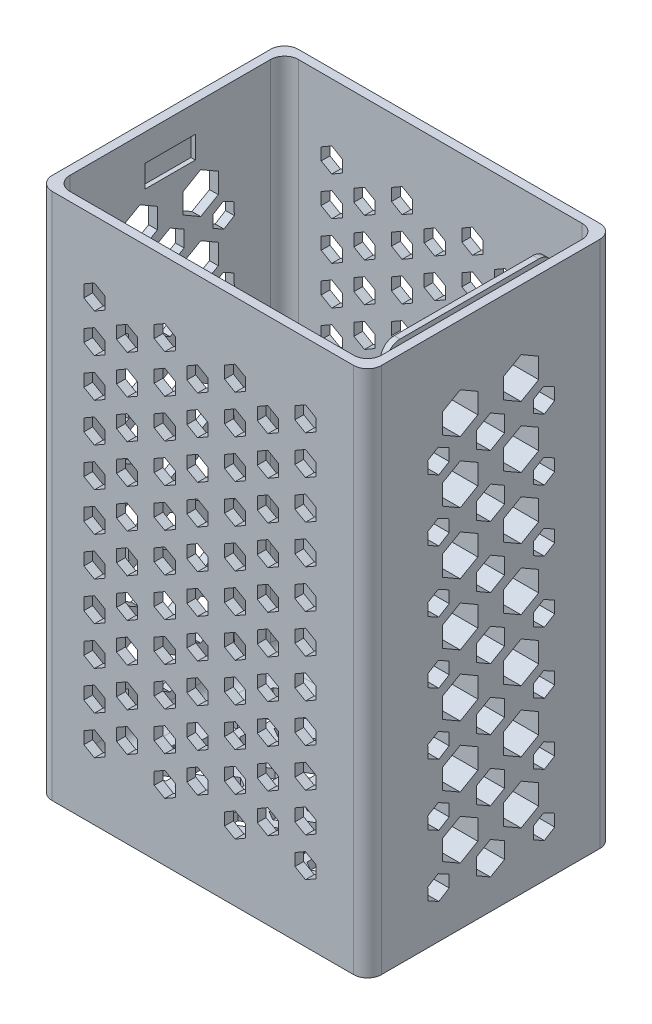
SolidWorks part; units mm, degrees
ref_plane "Front Plane" through (0, 0, 0) normal (0, 0, 1) x (1, 0, 0)
ref_plane "Top Plane" through (0, 0, 0) normal (0, 1, 0) x (1, 0, 0)
ref_plane "Right Plane" through (0, 0, 0) normal (1, 0, 0) x (0, 0, -1)
sketch "Sketch1" plane through (0, 0, 0) normal (0, 1, 0) x (1, 0, 0)
  line L0 (-6.35, 6.35) -> (-6.35, -171.3484)
  line L1 (0, 0) -> (224.9932, 0)
  line L2 (0, 0) -> (0, -164.9984)
  line L3 (0, -164.9984) -> (224.9932, -164.9984)
  line L4 (224.9932, 0) -> (224.9932, -164.9984)
  line L5 (-6.35, -171.3484) -> (231.3432, -171.3484)
  line L6 (231.3432, 6.35) -> (231.3432, -171.3484)
  line L7 (-6.35, 6.35) -> (231.3432, 6.35)
  dimension "D1" = 224.9932
  dimension "D2" = 164.9984
  dimension "D3" = 6.35
extrude "Boss-Extrude1" add sketch "Sketch1" along normal blind 374.65
sketch "Sketch4" plane through (224.9932, 0, 0) normal (-1, 0, 0) x (0, 0, 1)
  line L0 (164.9984, 0) -> (0, 0) construction
  line L1 (28.7274, 0) -> (136.1694, 0)
  line L2 (28.7274, 0) -> (28.7274, 374.65)
  line L3 (28.7274, 374.65) -> (136.1694, 374.65)
  line L4 (136.1694, 0) -> (136.1694, 374.65)
  line L5 (164.9984, 374.65) -> (0, 374.65) construction
  line L8 (164.9984, 374.65) -> (164.9984, 0) construction
  dimension "D1" = 107.442
  dimension "D2" = 28.829
extrude "Boss-Extrude2" add sketch "Sketch4" along normal blind 9.017
sketch "Sketch5" plane through (215.9762, 0, 0) normal (-1, 0, 0) x (0, 0, 1)
  line L0 (136.1694, 374.65) -> (28.7274, 374.65) construction
  line L5 (142.5194, 0) -> (22.3774, 0)
  line L6 (142.5194, 0) -> (142.5194, 374.65)
  line L7 (142.5194, 374.65) -> (22.3774, 374.65)
  line L8 (22.3774, 0) -> (22.3774, 374.65)
  line L9 (28.7274, 0) -> (136.1694, 0) construction
  line L11 (164.9984, 374.65) -> (164.9984, 0) construction
  line L12 (136.1694, 0) -> (136.1694, 374.65) construction
  line L13 (28.7274, 374.65) -> (28.7274, 0) construction
  dimension "D1" = 6.35
  dimension "D2" = 6.35
extrude "Boss-Extrude3" add sketch "Sketch5" along normal blind 4.191
sketch "Sketch7" plane through (0, 374.65, 0) normal (0, 1, 0) x (1, 0, 0)
  line L1 (215.9762, -136.1694) -> (224.9932, -136.1694)
  line L2 (215.9762, -136.1694) -> (215.9762, -28.7274)
  line L3 (215.9762, -28.7274) -> (224.9932, -28.7274)
  line L4 (224.9932, -136.1694) -> (224.9932, -28.7274)
extrude "Cut-Extrude1" cut sketch "Sketch7" against normal blind 21.59
sketch "Sketch10" plane through (0, 374.65, 0) normal (0, 1, 0) x (1, 0, 0)
  line L1 (211.7852, -142.5194) -> (215.9762, -142.5194)
  line L2 (211.7852, -142.5194) -> (211.7852, -22.3774)
  line L3 (211.7852, -22.3774) -> (215.9762, -22.3774)
  line L4 (215.9762, -142.5194) -> (215.9762, -22.3774)
extrude "Cut-Extrude2" cut sketch "Sketch10" against normal blind 5.588
fillet "Fillet1" radius 10 1 edges at (231.3432, 187.325, 171.3484)
fillet "Fillet2" radius 10 1 edges at (224.9932, 187.325, 164.9984)
fillet "Fillet3" radius 10 2 edges at (231.3432, 187.325, -6.35) (224.9932, 187.325, 0)
fillet "Fillet4" radius 10 2 edges at (-6.35, 187.325, 171.3484) (0, 187.325, 164.9984)
fillet "Fillet5" radius 10 2 edges at (0, 187.325, 0) (-6.35, 187.325, -6.35)
fillet "Fillet6" radius 10 2 edges at (220.4847, 353.06, 136.1694) (220.4847, 353.06, 28.7274)
fillet "Fillet7" radius 10 2 edges at (213.8807, 369.062, 22.3774) (213.8807, 369.062, 142.5194)
sketch "Sketch11" plane through (211.7852, 0, 0) normal (-1, 0, 0) x (0, 0, 1)
  line L0 (22.3774, 0) -> (142.5194, 0) construction
  line L1 (57.0484, 0) -> (107.8484, 0)
  line L2 (57.0484, 0) -> (57.0484, 15.24)
  line L3 (57.0484, 15.24) -> (107.8484, 15.24)
  line L4 (107.8484, 0) -> (107.8484, 15.24)
  line L5 (142.5194, 0) -> (142.5194, 359.062) construction
  dimension "D1" = 15.24
  dimension "D2" = 50.8
  dimension "D3" = 34.671
extrude "Boss-Extrude4" add sketch "Sketch11" along normal blind 19.9898
fillet "Fillet10" radius 10 2 edges at (191.7954, 7.62, 107.8484) (191.7954, 7.62, 57.0484)
fillet "Fillet11" radius 10 5 edges at (206.7903, 15.24, 107.8484) (194.7243, 15.24, 104.9195) (206.7903, 15.24, 57.0484) (194.7243, 15.24, 59.9773) (191.7954, 15.24, 82.4484)
sketch "Sketch12" plane through (0, 0, 0) normal (0, -1, 0) x (1, 0, 0)
  line L0 (231.3432, 161.3484) -> (231.3432, 3.65) construction
  line L1 (221.3432, -6.35) -> (3.65, -6.35) construction
  line L2 (-6.35, 3.65) -> (-6.35, 161.3484) construction
  line L3 (3.65, 171.3484) -> (221.3432, 171.3484) construction
  line L4 (231.3432, 161.3484) -> (231.3432, 3.65)
  line L5 (221.3432, -6.35) -> (3.65, -6.35)
  line L6 (-6.35, 3.65) -> (-6.35, 161.3484)
  line L7 (3.65, 171.3484) -> (221.3432, 171.3484)
  arc A0 (231.3432, 161.3484) -> (221.3432, 171.3484) centre (221.3432, 161.3484) ccw construction
  arc A1 (221.3432, -6.35) -> (231.3432, 3.65) centre (221.3432, 3.65) ccw construction
  arc A2 (-6.35, 3.65) -> (3.65, -6.35) centre (3.65, 3.65) ccw construction
  arc A3 (3.65, 171.3484) -> (-6.35, 161.3484) centre (3.65, 161.3484) ccw construction
  arc A4 (231.3432, 161.3484) -> (221.3432, 171.3484) centre (221.3432, 161.3484) ccw
  arc A5 (221.3432, -6.35) -> (231.3432, 3.65) centre (221.3432, 3.65) ccw
  arc A6 (-6.35, 3.65) -> (3.65, -6.35) centre (3.65, 3.65) ccw
  arc A7 (3.65, 171.3484) -> (-6.35, 161.3484) centre (3.65, 161.3484) ccw
extrude "Boss-Extrude5" add sketch "Sketch12" along normal blind 6.35
fillet "Fillet13" radius 10 9 edges at (224.9932, 0, 19.3637) (222.0643, 0, 2.9289) (112.4966, 0, 0) (2.9289, 0, 2.9289) (224.9932, 0, 145.5839) (222.0643, 0, 162.0695) (112.4966, 0, 164.9984) (2.9289, 0, 162.0695) (0, 0, 82.4992)
sketch "Sketch13" plane through (0, 0, 0) normal (1, 0, 0) x (0, 0, -1)
  line L0 (-10, 374.65) -> (-154.9984, 374.65) construction
  line L1 (-100.7542, 355.0412) -> (-64.356, 355.0412)
  line L2 (-100.7542, 355.0412) -> (-100.7542, 338.9122)
  line L3 (-100.7542, 338.9122) -> (-64.356, 338.9122)
  line L4 (-64.356, 355.0412) -> (-64.356, 338.9122)
  line L5 (-10, 10) -> (-10, 374.65) construction
  dimension "D1" = 19.6088
  dimension "D2" = 16.129
  dimension "D3" = 36.3982
  dimension "D4" = 54.356
extrude "Cut-Extrude4" cut sketch "Sketch13" against normal blind 3.175
sketch "Sketch15" plane through (0, -6.35, 0) normal (0, -1, 0) x (1, 0, 0)
  line L0 (177.8, 131.1399) -> (184.15, 134.8061)
  line L1 (196.85, 131.1399) -> (203.2, 134.8061)
  line L2 (203.2, 134.8061) -> (203.2, 142.1384)
  line L3 (203.2, 142.1384) -> (196.85, 145.8046)
  line L4 (196.85, 145.8046) -> (190.5, 142.1384)
  line L5 (190.5, 142.1384) -> (190.5, 134.8061)
  line L6 (190.5, 134.8061) -> (196.85, 131.1399)
  line L7 (171.45, 134.8061) -> (177.8, 131.1399)
  line L8 (171.45, 142.1384) -> (171.45, 134.8061)
  line L9 (177.8, 145.8046) -> (171.45, 142.1384)
  line L10 (184.15, 142.1384) -> (177.8, 145.8046)
  line L11 (184.15, 134.8061) -> (184.15, 142.1384)
  line L12 (158.75, 131.1399) -> (165.1, 134.8061)
  line L13 (152.4, 134.8061) -> (158.75, 131.1399)
  line L14 (152.4, 142.1384) -> (152.4, 134.8061)
  line L15 (158.75, 145.8046) -> (152.4, 142.1384)
  line L16 (165.1, 142.1384) -> (158.75, 145.8046)
  line L17 (165.1, 134.8061) -> (165.1, 142.1384)
  line L18 (139.7, 131.1399) -> (146.05, 134.8061)
  line L19 (133.35, 134.8061) -> (139.7, 131.1399)
  line L20 (133.35, 142.1384) -> (133.35, 134.8061)
  line L21 (139.7, 145.8046) -> (133.35, 142.1384)
  line L22 (146.05, 142.1384) -> (139.7, 145.8046)
  line L23 (146.05, 134.8061) -> (146.05, 142.1384)
  line L24 (120.65, 131.1399) -> (127, 134.8061)
  line L25 (114.3, 134.8061) -> (120.65, 131.1399)
  line L26 (114.3, 142.1384) -> (114.3, 134.8061)
  line L27 (120.65, 145.8046) -> (114.3, 142.1384)
  line L28 (127, 142.1384) -> (120.65, 145.8046)
  line L29 (127, 134.8061) -> (127, 142.1384)
  line L30 (-6.35, 161.3484) -> (-6.35, 3.65) construction
  line L31 (231.3432, 3.65) -> (231.3432, 161.3484) construction
  line L32 (3.65, -6.35) -> (221.3432, -6.35) construction
  line L38 (101.6, 131.1399) -> (107.95, 134.8061)
  line L39 (95.25, 134.8061) -> (101.6, 131.1399)
  line L40 (95.25, 142.1384) -> (95.25, 134.8061)
  line L41 (101.6, 145.8046) -> (95.25, 142.1384)
  line L42 (107.95, 142.1384) -> (101.6, 145.8046)
  line L43 (107.95, 134.8061) -> (107.95, 142.1384)
  line L44 (82.55, 131.1399) -> (88.9, 134.8061)
  line L45 (76.2, 134.8061) -> (82.55, 131.1399)
  line L46 (76.2, 142.1384) -> (76.2, 134.8061)
  line L47 (82.55, 145.8046) -> (76.2, 142.1384)
  line L48 (88.9, 142.1384) -> (82.55, 145.8046)
  line L49 (88.9, 134.8061) -> (88.9, 142.1384)
  line L50 (63.5, 131.1399) -> (69.85, 134.8061)
  line L51 (57.15, 134.8061) -> (63.5, 131.1399)
  line L52 (57.15, 142.1384) -> (57.15, 134.8061)
  line L53 (63.5, 145.8046) -> (57.15, 142.1384)
  line L54 (69.85, 142.1384) -> (63.5, 145.8046)
  line L55 (69.85, 134.8061) -> (69.85, 142.1384)
  line L56 (44.45, 131.1399) -> (50.8, 134.8061)
  line L57 (38.1, 134.8061) -> (44.45, 131.1399)
  line L58 (38.1, 142.1384) -> (38.1, 134.8061)
  line L59 (44.45, 145.8046) -> (38.1, 142.1384)
  line L60 (50.8, 142.1384) -> (44.45, 145.8046)
  line L61 (50.8, 134.8061) -> (50.8, 142.1384)
  line L62 (25.4, 131.1399) -> (31.75, 134.8061)
  line L63 (19.05, 134.8061) -> (25.4, 131.1399)
  line L64 (19.05, 142.1384) -> (19.05, 134.8061)
  line L65 (25.4, 145.8046) -> (19.05, 142.1384)
  line L66 (31.75, 142.1384) -> (25.4, 145.8046)
  line L67 (31.75, 134.8061) -> (31.75, 142.1384)
  line L74 (32.4716, 113.2256) -> (38.8216, 116.8918)
  line L75 (26.1216, 116.8918) -> (32.4716, 113.2256)
  line L76 (26.1216, 124.2241) -> (26.1216, 116.8918)
  line L77 (32.4716, 127.8903) -> (26.1216, 124.2241)
  line L78 (38.8216, 124.2241) -> (32.4716, 127.8903)
  line L79 (38.8216, 116.8918) -> (38.8216, 124.2241)
  line L80 (51.5216, 113.2256) -> (57.8716, 116.8918)
  line L81 (57.8716, 116.8918) -> (57.8716, 124.2241)
  line L82 (57.8716, 124.2241) -> (51.5216, 127.8903)
  line L83 (51.5216, 127.8903) -> (45.1716, 124.2241)
  line L84 (45.1716, 124.2241) -> (45.1716, 116.8918)
  line L85 (45.1716, 116.8918) -> (51.5216, 113.2256)
  line L86 (70.5716, 113.2256) -> (76.9216, 116.8918)
  line L87 (76.9216, 116.8918) -> (76.9216, 124.2241)
  line L88 (76.9216, 124.2241) -> (70.5716, 127.8903)
  line L89 (70.5716, 127.8903) -> (64.2216, 124.2241)
  line L90 (64.2216, 124.2241) -> (64.2216, 116.8918)
  line L91 (64.2216, 116.8918) -> (70.5716, 113.2256)
  line L92 (89.6216, 113.2256) -> (95.9716, 116.8918)
  line L93 (95.9716, 116.8918) -> (95.9716, 124.2241)
  line L94 (95.9716, 124.2241) -> (89.6216, 127.8903)
  line L95 (89.6216, 127.8903) -> (83.2716, 124.2241)
  line L96 (83.2716, 124.2241) -> (83.2716, 116.8918)
  line L97 (83.2716, 116.8918) -> (89.6216, 113.2256)
  line L98 (108.6716, 113.2256) -> (115.0216, 116.8918)
  line L99 (115.0216, 116.8918) -> (115.0216, 124.2241)
  line L100 (115.0216, 124.2241) -> (108.6716, 127.8903)
  line L101 (108.6716, 127.8903) -> (102.3216, 124.2241)
  line L102 (102.3216, 124.2241) -> (102.3216, 116.8918)
  line L103 (102.3216, 116.8918) -> (108.6716, 113.2256)
  line L104 (127.7216, 113.2256) -> (134.0716, 116.8918)
  line L105 (134.0716, 116.8918) -> (134.0716, 124.2241)
  line L106 (134.0716, 124.2241) -> (127.7216, 127.8903)
  line L107 (127.7216, 127.8903) -> (121.3716, 124.2241)
  line L108 (121.3716, 124.2241) -> (121.3716, 116.8918)
  line L109 (121.3716, 116.8918) -> (127.7216, 113.2256)
  line L110 (146.7716, 113.2256) -> (153.1216, 116.8918)
  line L111 (153.1216, 116.8918) -> (153.1216, 124.2241)
  line L112 (153.1216, 124.2241) -> (146.7716, 127.8903)
  line L113 (146.7716, 127.8903) -> (140.4216, 124.2241)
  line L114 (140.4216, 124.2241) -> (140.4216, 116.8918)
  line L115 (140.4216, 116.8918) -> (146.7716, 113.2256)
  line L116 (165.8216, 113.2256) -> (172.1716, 116.8918)
  line L117 (172.1716, 116.8918) -> (172.1716, 124.2241)
  line L118 (172.1716, 124.2241) -> (165.8216, 127.8903)
  line L119 (165.8216, 127.8903) -> (159.4716, 124.2241)
  line L120 (159.4716, 124.2241) -> (159.4716, 116.8918)
  line L121 (159.4716, 116.8918) -> (165.8216, 113.2256)
  line L122 (184.8716, 113.2256) -> (191.2216, 116.8918)
  line L123 (191.2216, 116.8918) -> (191.2216, 124.2241)
  line L124 (191.2216, 124.2241) -> (184.8716, 127.8903)
  line L125 (184.8716, 127.8903) -> (178.5216, 124.2241)
  line L126 (178.5216, 124.2241) -> (178.5216, 116.8918)
  line L127 (178.5216, 116.8918) -> (184.8716, 113.2256)
  line L128 (25.4, 95.3113) -> (31.75, 98.9775)
  line L129 (31.75, 98.9775) -> (31.75, 106.3099)
  line L130 (31.75, 106.3099) -> (25.4, 109.976)
  line L131 (25.4, 109.976) -> (19.05, 106.3099)
  line L132 (19.05, 106.3099) -> (19.05, 98.9775)
  line L133 (19.05, 98.9775) -> (25.4, 95.3113)
  line L134 (44.45, 95.3113) -> (50.8, 98.9775)
  line L135 (50.8, 98.9775) -> (50.8, 106.3099)
  line L136 (50.8, 106.3099) -> (44.45, 109.976)
  line L137 (44.45, 109.976) -> (38.1, 106.3099)
  line L138 (38.1, 106.3099) -> (38.1, 98.9775)
  line L139 (38.1, 98.9775) -> (44.45, 95.3113)
  line L140 (63.5, 95.3113) -> (69.85, 98.9775)
  line L141 (69.85, 98.9775) -> (69.85, 106.3099)
  line L142 (69.85, 106.3099) -> (63.5, 109.976)
  line L143 (63.5, 109.976) -> (57.15, 106.3099)
  line L144 (57.15, 106.3099) -> (57.15, 98.9775)
  line L145 (57.15, 98.9775) -> (63.5, 95.3113)
  line L146 (82.55, 95.3113) -> (88.9, 98.9775)
  line L147 (88.9, 98.9775) -> (88.9, 106.3099)
  line L148 (88.9, 106.3099) -> (82.55, 109.976)
  line L149 (82.55, 109.976) -> (76.2, 106.3099)
  line L150 (76.2, 106.3099) -> (76.2, 98.9775)
  line L151 (76.2, 98.9775) -> (82.55, 95.3113)
  line L152 (101.6, 95.3113) -> (107.95, 98.9775)
  line L153 (107.95, 98.9775) -> (107.95, 106.3099)
  line L154 (107.95, 106.3099) -> (101.6, 109.976)
  line L155 (101.6, 109.976) -> (95.25, 106.3099)
  line L156 (95.25, 106.3099) -> (95.25, 98.9775)
  line L157 (95.25, 98.9775) -> (101.6, 95.3113)
  line L158 (120.65, 95.3113) -> (127, 98.9775)
  line L159 (127, 98.9775) -> (127, 106.3099)
  line L160 (127, 106.3099) -> (120.65, 109.976)
  line L161 (120.65, 109.976) -> (114.3, 106.3099)
  line L162 (114.3, 106.3099) -> (114.3, 98.9775)
  line L163 (114.3, 98.9775) -> (120.65, 95.3113)
  line L164 (139.7, 95.3113) -> (146.05, 98.9775)
  line L165 (146.05, 98.9775) -> (146.05, 106.3099)
  line L166 (146.05, 106.3099) -> (139.7, 109.976)
  line L167 (139.7, 109.976) -> (133.35, 106.3099)
  line L168 (133.35, 106.3099) -> (133.35, 98.9775)
  line L169 (133.35, 98.9775) -> (139.7, 95.3113)
  line L170 (158.75, 95.3113) -> (165.1, 98.9775)
  line L171 (165.1, 98.9775) -> (165.1, 106.3099)
  line L172 (165.1, 106.3099) -> (158.75, 109.976)
  line L173 (158.75, 109.976) -> (152.4, 106.3099)
  line L174 (152.4, 106.3099) -> (152.4, 98.9775)
  line L175 (152.4, 98.9775) -> (158.75, 95.3113)
  line L176 (177.8, 95.3113) -> (184.15, 98.9775)
  line L177 (184.15, 98.9775) -> (184.15, 106.3099)
  line L178 (184.15, 106.3099) -> (177.8, 109.976)
  line L179 (177.8, 109.976) -> (171.45, 106.3099)
  line L180 (171.45, 106.3099) -> (171.45, 98.9775)
  line L181 (171.45, 98.9775) -> (177.8, 95.3113)
  line L188 (184.8716, 77.3971) -> (191.2216, 81.0632)
  line L189 (191.2216, 81.0632) -> (191.2216, 88.3956)
  line L190 (191.2216, 88.3956) -> (184.8716, 92.0618)
  line L191 (184.8716, 92.0618) -> (178.5216, 88.3956)
  line L192 (178.5216, 88.3956) -> (178.5216, 81.0632)
  line L193 (178.5216, 81.0632) -> (184.8716, 77.3971)
  line L194 (165.8216, 77.3971) -> (172.1716, 81.0632)
  line L195 (172.1716, 81.0632) -> (172.1716, 88.3956)
  line L196 (172.1716, 88.3956) -> (165.8216, 92.0618)
  line L197 (165.8216, 92.0618) -> (159.4716, 88.3956)
  line L198 (159.4716, 88.3956) -> (159.4716, 81.0632)
  line L199 (159.4716, 81.0632) -> (165.8216, 77.3971)
  line L200 (146.7716, 77.3971) -> (153.1216, 81.0632)
  line L201 (153.1216, 81.0632) -> (153.1216, 88.3956)
  line L202 (153.1216, 88.3956) -> (146.7716, 92.0618)
  line L203 (146.7716, 92.0618) -> (140.4216, 88.3956)
  line L204 (140.4216, 88.3956) -> (140.4216, 81.0632)
  line L205 (140.4216, 81.0632) -> (146.7716, 77.3971)
  line L206 (127.7216, 77.3971) -> (134.0716, 81.0632)
  line L207 (134.0716, 81.0632) -> (134.0716, 88.3956)
  line L208 (134.0716, 88.3956) -> (127.7216, 92.0618)
  line L209 (127.7216, 92.0618) -> (121.3716, 88.3956)
  line L210 (121.3716, 88.3956) -> (121.3716, 81.0632)
  line L211 (121.3716, 81.0632) -> (127.7216, 77.3971)
  line L212 (108.6716, 77.3971) -> (115.0216, 81.0632)
  line L213 (115.0216, 81.0632) -> (115.0216, 88.3956)
  line L214 (115.0216, 88.3956) -> (108.6716, 92.0618)
  line L215 (108.6716, 92.0618) -> (102.3216, 88.3956)
  line L216 (102.3216, 88.3956) -> (102.3216, 81.0632)
  line L217 (102.3216, 81.0632) -> (108.6716, 77.3971)
  line L218 (89.6216, 77.3971) -> (95.9716, 81.0632)
  line L219 (95.9716, 81.0632) -> (95.9716, 88.3956)
  line L220 (95.9716, 88.3956) -> (89.6216, 92.0618)
  line L221 (89.6216, 92.0618) -> (83.2716, 88.3956)
  line L222 (83.2716, 88.3956) -> (83.2716, 81.0632)
  line L223 (83.2716, 81.0632) -> (89.6216, 77.3971)
  line L224 (70.5716, 77.3971) -> (76.9216, 81.0632)
  line L225 (76.9216, 81.0632) -> (76.9216, 88.3956)
  line L226 (76.9216, 88.3956) -> (70.5716, 92.0618)
  line L227 (70.5716, 92.0618) -> (64.2216, 88.3956)
  line L228 (64.2216, 88.3956) -> (64.2216, 81.0632)
  line L229 (64.2216, 81.0632) -> (70.5716, 77.3971)
  line L230 (51.5216, 77.3971) -> (57.8716, 81.0632)
  line L231 (57.8716, 81.0632) -> (57.8716, 88.3956)
  line L232 (57.8716, 88.3956) -> (51.5216, 92.0618)
  line L233 (51.5216, 92.0618) -> (45.1716, 88.3956)
  line L234 (45.1716, 88.3956) -> (45.1716, 81.0632)
  line L235 (45.1716, 81.0632) -> (51.5216, 77.3971)
  line L236 (32.4716, 77.3971) -> (38.8216, 81.0632)
  line L237 (38.8216, 81.0632) -> (38.8216, 88.3956)
  line L238 (38.8216, 88.3956) -> (32.4716, 92.0618)
  line L239 (32.4716, 92.0618) -> (26.1216, 88.3956)
  line L240 (26.1216, 88.3956) -> (26.1216, 81.0632)
  line L241 (26.1216, 81.0632) -> (32.4716, 77.3971)
  line L242 (25.4, 59.4828) -> (31.75, 63.149)
  line L243 (31.75, 63.149) -> (31.75, 70.4813)
  line L244 (31.75, 70.4813) -> (25.4, 74.1475)
  line L245 (25.4, 74.1475) -> (19.05, 70.4813)
  line L246 (19.05, 70.4813) -> (19.05, 63.149)
  line L247 (19.05, 63.149) -> (25.4, 59.4828)
  line L248 (44.45, 59.4828) -> (50.8, 63.149)
  line L249 (50.8, 63.149) -> (50.8, 70.4813)
  line L250 (50.8, 70.4813) -> (44.45, 74.1475)
  line L251 (44.45, 74.1475) -> (38.1, 70.4813)
  line L252 (38.1, 70.4813) -> (38.1, 63.149)
  line L253 (38.1, 63.149) -> (44.45, 59.4828)
  line L254 (63.5, 59.4828) -> (69.85, 63.149)
  line L255 (69.85, 63.149) -> (69.85, 70.4813)
  line L256 (69.85, 70.4813) -> (63.5, 74.1475)
  line L257 (63.5, 74.1475) -> (57.15, 70.4813)
  line L258 (57.15, 70.4813) -> (57.15, 63.149)
  line L259 (57.15, 63.149) -> (63.5, 59.4828)
  line L260 (82.55, 59.4828) -> (88.9, 63.149)
  line L261 (88.9, 63.149) -> (88.9, 70.4813)
  line L262 (88.9, 70.4813) -> (82.55, 74.1475)
  line L263 (82.55, 74.1475) -> (76.2, 70.4813)
  line L264 (76.2, 70.4813) -> (76.2, 63.149)
  line L265 (76.2, 63.149) -> (82.55, 59.4828)
  line L266 (101.6, 59.4828) -> (107.95, 63.149)
  line L267 (107.95, 63.149) -> (107.95, 70.4813)
  line L268 (107.95, 70.4813) -> (101.6, 74.1475)
  line L269 (101.6, 74.1475) -> (95.25, 70.4813)
  line L270 (95.25, 70.4813) -> (95.25, 63.149)
  line L271 (95.25, 63.149) -> (101.6, 59.4828)
  line L272 (120.65, 59.4828) -> (127, 63.149)
  line L273 (127, 63.149) -> (127, 70.4813)
  line L274 (127, 70.4813) -> (120.65, 74.1475)
  line L275 (120.65, 74.1475) -> (114.3, 70.4813)
  line L276 (114.3, 70.4813) -> (114.3, 63.149)
  line L277 (114.3, 63.149) -> (120.65, 59.4828)
  line L278 (139.7, 59.4828) -> (146.05, 63.149)
  line L279 (146.05, 63.149) -> (146.05, 70.4813)
  line L280 (146.05, 70.4813) -> (139.7, 74.1475)
  line L281 (139.7, 74.1475) -> (133.35, 70.4813)
  line L282 (133.35, 70.4813) -> (133.35, 63.149)
  line L283 (133.35, 63.149) -> (139.7, 59.4828)
  line L284 (158.75, 59.4828) -> (165.1, 63.149)
  line L285 (165.1, 63.149) -> (165.1, 70.4813)
  line L286 (165.1, 70.4813) -> (158.75, 74.1475)
  line L287 (158.75, 74.1475) -> (152.4, 70.4813)
  line L288 (152.4, 70.4813) -> (152.4, 63.149)
  line L289 (152.4, 63.149) -> (158.75, 59.4828)
  line L290 (177.8, 59.4828) -> (184.15, 63.149)
  line L291 (184.15, 63.149) -> (184.15, 70.4813)
  line L292 (184.15, 70.4813) -> (177.8, 74.1475)
  line L293 (177.8, 74.1475) -> (171.45, 70.4813)
  line L294 (171.45, 70.4813) -> (171.45, 63.149)
  line L295 (171.45, 63.149) -> (177.8, 59.4828)
  line L302 (184.8716, 41.5685) -> (191.2216, 45.2347)
  line L303 (191.2216, 45.2347) -> (191.2216, 52.567)
  line L304 (191.2216, 52.567) -> (184.8716, 56.2332)
  line L305 (184.8716, 56.2332) -> (178.5216, 52.567)
  line L306 (178.5216, 52.567) -> (178.5216, 45.2347)
  line L307 (178.5216, 45.2347) -> (184.8716, 41.5685)
  line L308 (165.8216, 41.5685) -> (172.1716, 45.2347)
  line L309 (172.1716, 45.2347) -> (172.1716, 52.567)
  line L310 (172.1716, 52.567) -> (165.8216, 56.2332)
  line L311 (165.8216, 56.2332) -> (159.4716, 52.567)
  line L312 (159.4716, 52.567) -> (159.4716, 45.2347)
  line L313 (159.4716, 45.2347) -> (165.8216, 41.5685)
  line L314 (146.7716, 41.5685) -> (153.1216, 45.2347)
  line L315 (153.1216, 45.2347) -> (153.1216, 52.567)
  line L316 (153.1216, 52.567) -> (146.7716, 56.2332)
  line L317 (146.7716, 56.2332) -> (140.4216, 52.567)
  line L318 (140.4216, 52.567) -> (140.4216, 45.2347)
  line L319 (140.4216, 45.2347) -> (146.7716, 41.5685)
  line L320 (127.7216, 41.5685) -> (134.0716, 45.2347)
  line L321 (134.0716, 45.2347) -> (134.0716, 52.567)
  line L322 (134.0716, 52.567) -> (127.7216, 56.2332)
  line L323 (127.7216, 56.2332) -> (121.3716, 52.567)
  line L324 (121.3716, 52.567) -> (121.3716, 45.2347)
  line L325 (121.3716, 45.2347) -> (127.7216, 41.5685)
  line L326 (108.6716, 41.5685) -> (115.0216, 45.2347)
  line L327 (115.0216, 45.2347) -> (115.0216, 52.567)
  line L328 (115.0216, 52.567) -> (108.6716, 56.2332)
  line L329 (108.6716, 56.2332) -> (102.3216, 52.567)
  line L330 (102.3216, 52.567) -> (102.3216, 45.2347)
  line L331 (102.3216, 45.2347) -> (108.6716, 41.5685)
  line L332 (89.6216, 41.5685) -> (95.9716, 45.2347)
  line L333 (95.9716, 45.2347) -> (95.9716, 52.567)
  line L334 (95.9716, 52.567) -> (89.6216, 56.2332)
  line L335 (89.6216, 56.2332) -> (83.2716, 52.567)
  line L336 (83.2716, 52.567) -> (83.2716, 45.2347)
  line L337 (83.2716, 45.2347) -> (89.6216, 41.5685)
  line L338 (70.5716, 41.5685) -> (76.9216, 45.2347)
  line L339 (76.9216, 45.2347) -> (76.9216, 52.567)
  line L340 (76.9216, 52.567) -> (70.5716, 56.2332)
  line L341 (70.5716, 56.2332) -> (64.2216, 52.567)
  line L342 (64.2216, 52.567) -> (64.2216, 45.2347)
  line L343 (64.2216, 45.2347) -> (70.5716, 41.5685)
  line L344 (51.5216, 41.5685) -> (57.8716, 45.2347)
  line L345 (57.8716, 45.2347) -> (57.8716, 52.567)
  line L346 (57.8716, 52.567) -> (51.5216, 56.2332)
  line L347 (51.5216, 56.2332) -> (45.1716, 52.567)
  line L348 (45.1716, 52.567) -> (45.1716, 45.2347)
  line L349 (45.1716, 45.2347) -> (51.5216, 41.5685)
  line L350 (32.4716, 41.5685) -> (38.8216, 45.2347)
  line L351 (38.8216, 45.2347) -> (38.8216, 52.567)
  line L352 (38.8216, 52.567) -> (32.4716, 56.2332)
  line L353 (32.4716, 56.2332) -> (26.1216, 52.567)
  line L354 (26.1216, 52.567) -> (26.1216, 45.2347)
  line L355 (26.1216, 45.2347) -> (32.4716, 41.5685)
  line L356 (25.4, 23.6542) -> (31.75, 27.3204)
  line L357 (31.75, 27.3204) -> (31.75, 34.6528)
  line L358 (31.75, 34.6528) -> (25.4, 38.3189)
  line L359 (25.4, 38.3189) -> (19.05, 34.6528)
  line L360 (19.05, 34.6528) -> (19.05, 27.3204)
  line L361 (19.05, 27.3204) -> (25.4, 23.6542)
  line L362 (44.45, 23.6542) -> (50.8, 27.3204)
  line L363 (50.8, 27.3204) -> (50.8, 34.6528)
  line L364 (50.8, 34.6528) -> (44.45, 38.3189)
  line L365 (44.45, 38.3189) -> (38.1, 34.6528)
  line L366 (38.1, 34.6528) -> (38.1, 27.3204)
  line L367 (38.1, 27.3204) -> (44.45, 23.6542)
  line L368 (63.5, 23.6542) -> (69.85, 27.3204)
  line L369 (69.85, 27.3204) -> (69.85, 34.6528)
  line L370 (69.85, 34.6528) -> (63.5, 38.3189)
  line L371 (63.5, 38.3189) -> (57.15, 34.6528)
  line L372 (57.15, 34.6528) -> (57.15, 27.3204)
  line L373 (57.15, 27.3204) -> (63.5, 23.6542)
  line L374 (82.55, 23.6542) -> (88.9, 27.3204)
  line L375 (88.9, 27.3204) -> (88.9, 34.6528)
  line L376 (88.9, 34.6528) -> (82.55, 38.3189)
  line L377 (82.55, 38.3189) -> (76.2, 34.6528)
  line L378 (76.2, 34.6528) -> (76.2, 27.3204)
  line L379 (76.2, 27.3204) -> (82.55, 23.6542)
  line L380 (101.6, 23.6542) -> (107.95, 27.3204)
  line L381 (107.95, 27.3204) -> (107.95, 34.6528)
  line L382 (107.95, 34.6528) -> (101.6, 38.3189)
  line L383 (101.6, 38.3189) -> (95.25, 34.6528)
  line L384 (95.25, 34.6528) -> (95.25, 27.3204)
  line L385 (95.25, 27.3204) -> (101.6, 23.6542)
  line L386 (120.65, 23.6542) -> (127, 27.3204)
  line L387 (127, 27.3204) -> (127, 34.6528)
  line L388 (127, 34.6528) -> (120.65, 38.3189)
  line L389 (120.65, 38.3189) -> (114.3, 34.6528)
  line L390 (114.3, 34.6528) -> (114.3, 27.3204)
  line L391 (114.3, 27.3204) -> (120.65, 23.6542)
  line L392 (139.7, 23.6542) -> (146.05, 27.3204)
  line L393 (146.05, 27.3204) -> (146.05, 34.6528)
  line L394 (146.05, 34.6528) -> (139.7, 38.3189)
  line L395 (139.7, 38.3189) -> (133.35, 34.6528)
  line L396 (133.35, 34.6528) -> (133.35, 27.3204)
  line L397 (133.35, 27.3204) -> (139.7, 23.6542)
  line L398 (158.75, 23.6542) -> (165.1, 27.3204)
  line L399 (165.1, 27.3204) -> (165.1, 34.6528)
  line L400 (165.1, 34.6528) -> (158.75, 38.3189)
  line L401 (158.75, 38.3189) -> (152.4, 34.6528)
  line L402 (152.4, 34.6528) -> (152.4, 27.3204)
  line L403 (152.4, 27.3204) -> (158.75, 23.6542)
  line L404 (177.8, 23.6542) -> (184.15, 27.3204)
  line L405 (184.15, 27.3204) -> (184.15, 34.6528)
  line L406 (184.15, 34.6528) -> (177.8, 38.3189)
  line L407 (177.8, 38.3189) -> (171.45, 34.6528)
  line L408 (171.45, 34.6528) -> (171.45, 27.3204)
  line L409 (171.45, 27.3204) -> (177.8, 23.6542)
  line L410 (196.85, 23.6542) -> (203.2, 27.3204)
  line L411 (203.2, 27.3204) -> (203.2, 34.6528)
  line L412 (203.2, 34.6528) -> (196.85, 38.3189)
  line L413 (196.85, 38.3189) -> (190.5, 34.6528)
  line L414 (190.5, 34.6528) -> (190.5, 27.3204)
  line L415 (190.5, 27.3204) -> (196.85, 23.6542)
  line L416 (190.5, 106.3099) -> (190.5, 98.9775) [skipped]
  line L417 (190.5, 98.9775) -> (196.85, 95.3113) [skipped]
  line L418 (196.85, 95.3113) -> (203.2, 98.9775) [skipped]
  line L419 (203.2, 98.9775) -> (203.2, 106.3099) [skipped]
  line L420 (203.2, 106.3099) -> (196.85, 109.976) [skipped]
  line L421 (196.85, 109.976) -> (190.5, 106.3099) [skipped]
  line L422 (203.2, 63.149) -> (203.2, 70.4813) [skipped]
  line L423 (196.85, 59.4828) -> (203.2, 63.149) [skipped]
  line L424 (190.5, 63.149) -> (196.85, 59.4828) [skipped]
  line L425 (190.5, 70.4813) -> (190.5, 63.149) [skipped]
  line L426 (196.85, 74.1475) -> (190.5, 70.4813) [skipped]
  line L427 (203.2, 70.4813) -> (196.85, 74.1475) [skipped]
  circle A0 centre (196.85, 138.4722) radius 6.35 construction
  dimension "D2" = 25.4
  dimension "D4" = 6.35
  dimension "D5" = 6.35
  dimension "D7" = 28.1432
  dimension "D8" = 7.3323
  dimension "D10" = 6.35
  dimension "D12" = 6.35
  dimension "D13" = 30.0042
  dimension "D14" = 40.1216
  dimension "D15" = 32.4716
  dimension "D16" = 6.35
  dimension "D17" = 9.525
  dimension "D18" = 9.525
  dimension "D3" = 10
  dimension "D6" = 9
  dimension "D9" = 3
  dimension "D11" = 2
sketch "Sketch17" plane through (0, -6.35, 0) normal (0, -1, 0) x (1, 0, 0)
extrude "Cut-Extrude5" cut sketch "Sketch15" against normal blind 6.35
sketch "Sketch18" plane through (211.7852, 0, 0) normal (-1, 0, 0) x (0, 0, 1)
  line L0 (73.1774, 323.6297) -> (60.4774, 330.962)
  line L1 (117.1194, 323.6297) -> (104.4194, 330.962)
  line L2 (104.4194, 330.962) -> (91.7194, 323.6297)
  line L3 (91.7194, 323.6297) -> (91.7194, 308.965)
  line L4 (91.7194, 308.965) -> (104.4194, 301.6326)
  line L5 (104.4194, 301.6326) -> (117.1194, 308.965)
  line L6 (117.1194, 308.965) -> (117.1194, 323.6297)
  line L7 (142.5194, 0) -> (142.5194, 359.062) construction
  line L8 (32.3774, 369.062) -> (132.5194, 369.062) construction
  line L9 (60.4774, 330.962) -> (47.7774, 323.6297)
  line L10 (47.7774, 323.6297) -> (47.7774, 308.965)
  line L11 (47.7774, 308.965) -> (60.4774, 301.6326)
  line L12 (60.4774, 301.6326) -> (73.1774, 308.965)
  line L13 (73.1774, 308.965) -> (73.1774, 323.6297)
  line L14 (73.1774, 279.1797) -> (60.4774, 286.512)
  line L15 (60.4774, 286.512) -> (47.7774, 279.1797)
  line L16 (47.7774, 279.1797) -> (47.7774, 264.515)
  line L17 (47.7774, 264.515) -> (60.4774, 257.1826)
  line L18 (60.4774, 257.1826) -> (73.1774, 264.515)
  line L19 (73.1774, 264.515) -> (73.1774, 279.1797)
  line L20 (73.1774, 234.7297) -> (60.4774, 242.062)
  line L21 (60.4774, 242.062) -> (47.7774, 234.7297)
  line L22 (47.7774, 234.7297) -> (47.7774, 220.065)
  line L23 (47.7774, 220.065) -> (60.4774, 212.7326)
  line L24 (60.4774, 212.7326) -> (73.1774, 220.065)
  line L25 (73.1774, 220.065) -> (73.1774, 234.7297)
  line L26 (73.1774, 190.2797) -> (60.4774, 197.612)
  line L27 (60.4774, 197.612) -> (47.7774, 190.2797)
  line L28 (47.7774, 190.2797) -> (47.7774, 175.615)
  line L29 (47.7774, 175.615) -> (60.4774, 168.2826)
  line L30 (60.4774, 168.2826) -> (73.1774, 175.615)
  line L31 (73.1774, 175.615) -> (73.1774, 190.2797)
  line L32 (73.1774, 145.8297) -> (60.4774, 153.162)
  line L33 (60.4774, 153.162) -> (47.7774, 145.8297)
  line L34 (47.7774, 145.8297) -> (47.7774, 131.165)
  line L35 (47.7774, 131.165) -> (60.4774, 123.8326)
  line L36 (60.4774, 123.8326) -> (73.1774, 131.165)
  line L37 (73.1774, 131.165) -> (73.1774, 145.8297)
  line L38 (73.1774, 101.3797) -> (60.4774, 108.712)
  line L39 (60.4774, 108.712) -> (47.7774, 101.3797)
  line L40 (47.7774, 101.3797) -> (47.7774, 86.715)
  line L41 (47.7774, 86.715) -> (60.4774, 79.3826)
  line L42 (60.4774, 79.3826) -> (73.1774, 86.715)
  line L43 (73.1774, 86.715) -> (73.1774, 101.3797)
  line L44 (73.1774, 56.9297) -> (60.4774, 64.262)
  line L45 (60.4774, 64.262) -> (47.7774, 56.9297)
  line L46 (47.7774, 56.9297) -> (47.7774, 42.265)
  line L47 (47.7774, 42.265) -> (60.4774, 34.9326)
  line L48 (60.4774, 34.9326) -> (73.1774, 42.265)
  line L49 (73.1774, 42.265) -> (73.1774, 56.9297)
  line L56 (117.1194, 279.1797) -> (104.4194, 286.512)
  line L57 (104.4194, 286.512) -> (91.7194, 279.1797)
  line L58 (91.7194, 279.1797) -> (91.7194, 264.515)
  line L59 (91.7194, 264.515) -> (104.4194, 257.1826)
  line L60 (104.4194, 257.1826) -> (117.1194, 264.515)
  line L61 (117.1194, 264.515) -> (117.1194, 279.1797)
  line L62 (117.1194, 234.7297) -> (104.4194, 242.062)
  line L63 (104.4194, 242.062) -> (91.7194, 234.7297)
  line L64 (91.7194, 234.7297) -> (91.7194, 220.065)
  line L65 (91.7194, 220.065) -> (104.4194, 212.7326)
  line L66 (104.4194, 212.7326) -> (117.1194, 220.065)
  line L67 (117.1194, 220.065) -> (117.1194, 234.7297)
  line L68 (117.1194, 190.2797) -> (104.4194, 197.612)
  line L69 (104.4194, 197.612) -> (91.7194, 190.2797)
  line L70 (91.7194, 190.2797) -> (91.7194, 175.615)
  line L71 (91.7194, 175.615) -> (104.4194, 168.2826)
  line L72 (104.4194, 168.2826) -> (117.1194, 175.615)
  line L73 (117.1194, 175.615) -> (117.1194, 190.2797)
  line L74 (117.1194, 145.8297) -> (104.4194, 153.162)
  line L75 (104.4194, 153.162) -> (91.7194, 145.8297)
  line L76 (91.7194, 145.8297) -> (91.7194, 131.165)
  line L77 (91.7194, 131.165) -> (104.4194, 123.8326)
  line L78 (104.4194, 123.8326) -> (117.1194, 131.165)
  line L79 (117.1194, 131.165) -> (117.1194, 145.8297)
  line L80 (117.1194, 101.3797) -> (104.4194, 108.712)
  line L81 (104.4194, 108.712) -> (91.7194, 101.3797)
  line L82 (91.7194, 101.3797) -> (91.7194, 86.715)
  line L83 (91.7194, 86.715) -> (104.4194, 79.3826)
  line L84 (104.4194, 79.3826) -> (117.1194, 86.715)
  line L85 (117.1194, 86.715) -> (117.1194, 101.3797)
  line L86 (117.1194, 56.9297) -> (104.4194, 64.262)
  line L87 (104.4194, 64.262) -> (91.7194, 56.9297)
  line L88 (91.7194, 56.9297) -> (91.7194, 42.265)
  line L89 (91.7194, 42.265) -> (104.4194, 34.9326)
  line L90 (104.4194, 34.9326) -> (117.1194, 42.265)
  line L91 (117.1194, 42.265) -> (117.1194, 56.9297)
  line L98 (22.3774, 359.062) -> (22.3774, 0) construction
  line L99 (91.7194, 12.4797) -> (91.7194, -2.185) [skipped]
  line L100 (91.7194, -2.185) -> (104.4194, -9.5174) [skipped]
  line L101 (104.4194, -9.5174) -> (117.1194, -2.185) [skipped]
  line L102 (117.1194, 12.4797) -> (104.4194, 19.812) [skipped]
  line L103 (117.1194, -2.185) -> (117.1194, 12.4797) [skipped]
  line L104 (104.4194, 19.812) -> (91.7194, 12.4797) [skipped]
  line L105 (73.1774, -2.185) -> (73.1774, 12.4797) [skipped]
  line L106 (60.4774, -9.5174) -> (73.1774, -2.185) [skipped]
  line L107 (47.7774, -2.185) -> (60.4774, -9.5174) [skipped]
  line L108 (47.7774, 12.4797) -> (47.7774, -2.185) [skipped]
  line L109 (60.4774, 19.812) -> (47.7774, 12.4797) [skipped]
  line L110 (73.1774, 12.4797) -> (60.4774, 19.812) [skipped]
  circle A0 centre (104.4194, 316.2973) radius 12.7 construction
  dimension "D2" = 25.4
  dimension "D1" = 25.4
  dimension "D3" = 38.1
  dimension "D6" = 25.4
  dimension "D4" = 2
  dimension "D5" = 8
extrude "Cut-Extrude6" cut sketch "Sketch18" against normal through all and the other way through all
sketch "Sketch22" plane through (-6.35, 0, 0) normal (-1, 0, 0) x (0, 0, 1)
sketch "Sketch23" plane through (0, 0, 171.3484) normal (0, 0, 1) x (1, 0, 0)
  line L0 (3.65, 374.65) -> (221.3432, 374.65) construction
  line L1 (34.13, 315.0512) -> (41.75, 319.4506)
  line L2 (41.75, 319.4506) -> (41.75, 328.2494)
  line L3 (41.75, 328.2494) -> (34.13, 332.6488)
  line L4 (34.13, 332.6488) -> (26.51, 328.2494)
  line L5 (26.51, 328.2494) -> (26.51, 319.4506)
  line L6 (26.51, 319.4506) -> (34.13, 315.0512)
  line L7 (3.65, 374.65) -> (3.65, -6.35) construction
  line L8 (41.75, 300.3094) -> (34.13, 304.7088)
  line L9 (34.13, 304.7088) -> (26.51, 300.3094)
  line L10 (26.51, 300.3094) -> (26.51, 291.5106)
  line L11 (26.51, 291.5106) -> (34.13, 287.1112)
  line L12 (41.75, 291.5106) -> (41.75, 300.3094)
  line L13 (34.13, 287.1112) -> (41.75, 291.5106)
  line L14 (41.75, 272.3694) -> (34.13, 276.7688)
  line L15 (34.13, 276.7688) -> (26.51, 272.3694)
  line L16 (26.51, 272.3694) -> (26.51, 263.5706)
  line L17 (26.51, 263.5706) -> (34.13, 259.1712)
  line L18 (41.75, 263.5706) -> (41.75, 272.3694)
  line L19 (34.13, 259.1712) -> (41.75, 263.5706)
  line L20 (41.75, 244.4294) -> (34.13, 248.8288)
  line L21 (34.13, 248.8288) -> (26.51, 244.4294)
  line L22 (26.51, 244.4294) -> (26.51, 235.6306)
  line L23 (26.51, 235.6306) -> (34.13, 231.2312)
  line L24 (41.75, 235.6306) -> (41.75, 244.4294)
  line L25 (34.13, 231.2312) -> (41.75, 235.6306)
  line L26 (41.75, 216.4894) -> (34.13, 220.8888)
  line L27 (34.13, 220.8888) -> (26.51, 216.4894)
  line L28 (26.51, 216.4894) -> (26.51, 207.6906)
  line L29 (26.51, 207.6906) -> (34.13, 203.2912)
  line L30 (41.75, 207.6906) -> (41.75, 216.4894)
  line L31 (34.13, 203.2912) -> (41.75, 207.6906)
  line L32 (41.75, 188.5494) -> (34.13, 192.9488)
  line L33 (34.13, 192.9488) -> (26.51, 188.5494)
  line L34 (26.51, 188.5494) -> (26.51, 179.7506)
  line L35 (26.51, 179.7506) -> (34.13, 175.3512)
  line L36 (41.75, 179.7506) -> (41.75, 188.5494)
  line L37 (34.13, 175.3512) -> (41.75, 179.7506)
  line L38 (41.75, 160.6094) -> (34.13, 165.0088)
  line L39 (34.13, 165.0088) -> (26.51, 160.6094)
  line L40 (26.51, 160.6094) -> (26.51, 151.8106)
  line L41 (26.51, 151.8106) -> (34.13, 147.4112)
  line L42 (41.75, 151.8106) -> (41.75, 160.6094)
  line L43 (34.13, 147.4112) -> (41.75, 151.8106)
  line L44 (41.75, 132.6694) -> (34.13, 137.0688)
  line L45 (34.13, 137.0688) -> (26.51, 132.6694)
  line L46 (26.51, 132.6694) -> (26.51, 123.8706)
  line L47 (26.51, 123.8706) -> (34.13, 119.4712)
  line L48 (41.75, 123.8706) -> (41.75, 132.6694)
  line L49 (34.13, 119.4712) -> (41.75, 123.8706)
  line L50 (41.75, 104.7294) -> (34.13, 109.1288)
  line L51 (34.13, 109.1288) -> (26.51, 104.7294)
  line L52 (26.51, 104.7294) -> (26.51, 95.9306)
  line L53 (26.51, 95.9306) -> (34.13, 91.5312)
  line L54 (41.75, 95.9306) -> (41.75, 104.7294)
  line L55 (34.13, 91.5312) -> (41.75, 95.9306)
  line L56 (41.75, 76.7894) -> (34.13, 81.1888)
  line L57 (34.13, 81.1888) -> (26.51, 76.7894)
  line L58 (26.51, 76.7894) -> (26.51, 67.9906)
  line L59 (26.51, 67.9906) -> (34.13, 63.5912)
  line L60 (41.75, 67.9906) -> (41.75, 76.7894)
  line L61 (34.13, 63.5912) -> (41.75, 67.9906)
  line L62 (41.75, 48.8494) -> (34.13, 53.2488)
  line L63 (34.13, 53.2488) -> (26.51, 48.8494)
  line L64 (26.51, 48.8494) -> (26.51, 40.0506)
  line L65 (26.51, 40.0506) -> (34.13, 35.6512)
  line L66 (41.75, 40.0506) -> (41.75, 48.8494)
  line L67 (34.13, 35.6512) -> (41.75, 40.0506)
  line L68 (65.3762, 314.1873) -> (57.7562, 318.5867)
  line L69 (57.7562, 318.5867) -> (50.1362, 314.1873)
  line L70 (50.1362, 314.1873) -> (50.1362, 305.3885)
  line L71 (50.1362, 305.3885) -> (57.7562, 300.9891)
  line L72 (65.3762, 305.3885) -> (65.3762, 314.1873)
  line L73 (57.7562, 300.9891) -> (65.3762, 305.3885)
  line L74 (65.3762, 286.2473) -> (57.7562, 290.6467)
  line L75 (57.7562, 290.6467) -> (50.1362, 286.2473)
  line L76 (50.1362, 286.2473) -> (50.1362, 277.4485)
  line L77 (50.1362, 277.4485) -> (57.7562, 273.0491)
  line L78 (65.3762, 277.4485) -> (65.3762, 286.2473)
  line L79 (57.7562, 273.0491) -> (65.3762, 277.4485)
  line L80 (65.3762, 258.3073) -> (57.7562, 262.7067)
  line L81 (57.7562, 262.7067) -> (50.1362, 258.3073)
  line L82 (50.1362, 258.3073) -> (50.1362, 249.5085)
  line L83 (50.1362, 249.5085) -> (57.7562, 245.1091)
  line L84 (65.3762, 249.5085) -> (65.3762, 258.3073)
  line L85 (57.7562, 245.1091) -> (65.3762, 249.5085)
  line L86 (65.3762, 230.3673) -> (57.7562, 234.7667)
  line L87 (57.7562, 234.7667) -> (50.1362, 230.3673)
  line L88 (50.1362, 230.3673) -> (50.1362, 221.5685)
  line L89 (50.1362, 221.5685) -> (57.7562, 217.1691)
  line L90 (65.3762, 221.5685) -> (65.3762, 230.3673)
  line L91 (57.7562, 217.1691) -> (65.3762, 221.5685)
  line L92 (65.3762, 202.4273) -> (57.7562, 206.8267)
  line L93 (57.7562, 206.8267) -> (50.1362, 202.4273)
  line L94 (50.1362, 202.4273) -> (50.1362, 193.6285)
  line L95 (50.1362, 193.6285) -> (57.7562, 189.2291)
  line L96 (65.3762, 193.6285) -> (65.3762, 202.4273)
  line L97 (57.7562, 189.2291) -> (65.3762, 193.6285)
  line L98 (65.3762, 174.4873) -> (57.7562, 178.8867)
  line L99 (57.7562, 178.8867) -> (50.1362, 174.4873)
  line L100 (50.1362, 174.4873) -> (50.1362, 165.6885)
  line L101 (50.1362, 165.6885) -> (57.7562, 161.2891)
  line L102 (65.3762, 165.6885) -> (65.3762, 174.4873)
  line L103 (57.7562, 161.2891) -> (65.3762, 165.6885)
  line L104 (65.3762, 146.5473) -> (57.7562, 150.9467)
  line L105 (57.7562, 150.9467) -> (50.1362, 146.5473)
  line L106 (50.1362, 146.5473) -> (50.1362, 137.7485)
  line L107 (50.1362, 137.7485) -> (57.7562, 133.3491)
  line L108 (65.3762, 137.7485) -> (65.3762, 146.5473)
  line L109 (57.7562, 133.3491) -> (65.3762, 137.7485)
  line L110 (65.3762, 118.6073) -> (57.7562, 123.0067)
  line L111 (57.7562, 123.0067) -> (50.1362, 118.6073)
  line L112 (50.1362, 118.6073) -> (50.1362, 109.8085)
  line L113 (50.1362, 109.8085) -> (57.7562, 105.4091)
  line L114 (65.3762, 109.8085) -> (65.3762, 118.6073)
  line L115 (57.7562, 105.4091) -> (65.3762, 109.8085)
  line L116 (65.3762, 90.6673) -> (57.7562, 95.0667)
  line L117 (57.7562, 95.0667) -> (50.1362, 90.6673)
  line L118 (50.1362, 90.6673) -> (50.1362, 81.8685)
  line L119 (50.1362, 81.8685) -> (57.7562, 77.4691)
  line L120 (65.3762, 81.8685) -> (65.3762, 90.6673)
  line L121 (57.7562, 77.4691) -> (65.3762, 81.8685)
  line L122 (65.3762, 62.7273) -> (57.7562, 67.1267)
  line L123 (57.7562, 67.1267) -> (50.1362, 62.7273)
  line L124 (50.1362, 62.7273) -> (50.1362, 53.9285)
  line L125 (50.1362, 53.9285) -> (57.7562, 49.5291)
  line L126 (65.3762, 53.9285) -> (65.3762, 62.7273)
  line L127 (57.7562, 49.5291) -> (65.3762, 53.9285)
  line L128 (84.93, 315.0512) -> (92.55, 319.4506)
  line L129 (92.55, 319.4506) -> (92.55, 328.2494)
  line L130 (92.55, 328.2494) -> (84.93, 332.6488)
  line L131 (84.93, 332.6488) -> (77.31, 328.2494)
  line L132 (77.31, 328.2494) -> (77.31, 319.4506)
  line L133 (77.31, 319.4506) -> (84.93, 315.0512)
  line L134 (92.55, 300.3094) -> (84.93, 304.7088)
  line L135 (84.93, 304.7088) -> (77.31, 300.3094)
  line L136 (77.31, 300.3094) -> (77.31, 291.5106)
  line L137 (77.31, 291.5106) -> (84.93, 287.1112)
  line L138 (92.55, 291.5106) -> (92.55, 300.3094)
  line L139 (84.93, 287.1112) -> (92.55, 291.5106)
  line L140 (92.55, 272.3694) -> (84.93, 276.7688)
  line L141 (84.93, 276.7688) -> (77.31, 272.3694)
  line L142 (77.31, 272.3694) -> (77.31, 263.5706)
  line L143 (77.31, 263.5706) -> (84.93, 259.1712)
  line L144 (92.55, 263.5706) -> (92.55, 272.3694)
  line L145 (84.93, 259.1712) -> (92.55, 263.5706)
  line L146 (92.55, 244.4294) -> (84.93, 248.8288)
  line L147 (84.93, 248.8288) -> (77.31, 244.4294)
  line L148 (77.31, 244.4294) -> (77.31, 235.6306)
  line L149 (77.31, 235.6306) -> (84.93, 231.2312)
  line L150 (92.55, 235.6306) -> (92.55, 244.4294)
  line L151 (84.93, 231.2312) -> (92.55, 235.6306)
  line L152 (92.55, 216.4894) -> (84.93, 220.8888)
  line L153 (84.93, 220.8888) -> (77.31, 216.4894)
  line L154 (77.31, 216.4894) -> (77.31, 207.6906)
  line L155 (77.31, 207.6906) -> (84.93, 203.2912)
  line L156 (92.55, 207.6906) -> (92.55, 216.4894)
  line L157 (84.93, 203.2912) -> (92.55, 207.6906)
  line L158 (92.55, 188.5494) -> (84.93, 192.9488)
  line L159 (84.93, 192.9488) -> (77.31, 188.5494)
  line L160 (77.31, 188.5494) -> (77.31, 179.7506)
  line L161 (77.31, 179.7506) -> (84.93, 175.3512)
  line L162 (92.55, 179.7506) -> (92.55, 188.5494)
  line L163 (84.93, 175.3512) -> (92.55, 179.7506)
  line L164 (92.55, 160.6094) -> (84.93, 165.0088)
  line L165 (84.93, 165.0088) -> (77.31, 160.6094)
  line L166 (77.31, 160.6094) -> (77.31, 151.8106)
  line L167 (77.31, 151.8106) -> (84.93, 147.4112)
  line L168 (92.55, 151.8106) -> (92.55, 160.6094)
  line L169 (84.93, 147.4112) -> (92.55, 151.8106)
  line L170 (92.55, 132.6694) -> (84.93, 137.0688)
  line L171 (84.93, 137.0688) -> (77.31, 132.6694)
  line L172 (77.31, 132.6694) -> (77.31, 123.8706)
  line L173 (77.31, 123.8706) -> (84.93, 119.4712)
  line L174 (92.55, 123.8706) -> (92.55, 132.6694)
  line L175 (84.93, 119.4712) -> (92.55, 123.8706)
  line L176 (92.55, 104.7294) -> (84.93, 109.1288)
  line L177 (84.93, 109.1288) -> (77.31, 104.7294)
  line L178 (77.31, 104.7294) -> (77.31, 95.9306)
  line L179 (77.31, 95.9306) -> (84.93, 91.5312)
  line L180 (92.55, 95.9306) -> (92.55, 104.7294)
  line L181 (84.93, 91.5312) -> (92.55, 95.9306)
  line L182 (92.55, 76.7894) -> (84.93, 81.1888)
  line L183 (84.93, 81.1888) -> (77.31, 76.7894)
  line L184 (77.31, 76.7894) -> (77.31, 67.9906)
  line L185 (77.31, 67.9906) -> (84.93, 63.5912)
  line L186 (92.55, 67.9906) -> (92.55, 76.7894)
  line L187 (84.93, 63.5912) -> (92.55, 67.9906)
  line L188 (92.55, 48.8494) -> (84.93, 53.2488)
  line L189 (84.93, 53.2488) -> (77.31, 48.8494)
  line L190 (77.31, 48.8494) -> (77.31, 40.0506)
  line L191 (77.31, 40.0506) -> (84.93, 35.6512)
  line L192 (92.55, 40.0506) -> (92.55, 48.8494)
  line L193 (84.93, 35.6512) -> (92.55, 40.0506)
  line L194 (116.1762, 314.1873) -> (108.5562, 318.5867)
  line L195 (108.5562, 318.5867) -> (100.9362, 314.1873)
  line L196 (100.9362, 314.1873) -> (100.9362, 305.3885)
  line L197 (100.9362, 305.3885) -> (108.5562, 300.9891)
  line L198 (116.1762, 305.3885) -> (116.1762, 314.1873)
  line L199 (108.5562, 300.9891) -> (116.1762, 305.3885)
  line L200 (116.1762, 286.2473) -> (108.5562, 290.6467)
  line L201 (108.5562, 290.6467) -> (100.9362, 286.2473)
  line L202 (100.9362, 286.2473) -> (100.9362, 277.4485)
  line L203 (100.9362, 277.4485) -> (108.5562, 273.0491)
  line L204 (116.1762, 277.4485) -> (116.1762, 286.2473)
  line L205 (108.5562, 273.0491) -> (116.1762, 277.4485)
  line L206 (116.1762, 258.3073) -> (108.5562, 262.7067)
  line L207 (108.5562, 262.7067) -> (100.9362, 258.3073)
  line L208 (100.9362, 258.3073) -> (100.9362, 249.5085)
  line L209 (100.9362, 249.5085) -> (108.5562, 245.1091)
  line L210 (116.1762, 249.5085) -> (116.1762, 258.3073)
  line L211 (108.5562, 245.1091) -> (116.1762, 249.5085)
  line L212 (116.1762, 230.3673) -> (108.5562, 234.7667)
  line L213 (108.5562, 234.7667) -> (100.9362, 230.3673)
  line L214 (100.9362, 230.3673) -> (100.9362, 221.5685)
  line L215 (100.9362, 221.5685) -> (108.5562, 217.1691)
  line L216 (116.1762, 221.5685) -> (116.1762, 230.3673)
  line L217 (108.5562, 217.1691) -> (116.1762, 221.5685)
  line L218 (116.1762, 202.4273) -> (108.5562, 206.8267)
  line L219 (108.5562, 206.8267) -> (100.9362, 202.4273)
  line L220 (100.9362, 202.4273) -> (100.9362, 193.6285)
  line L221 (100.9362, 193.6285) -> (108.5562, 189.2291)
  line L222 (116.1762, 193.6285) -> (116.1762, 202.4273)
  line L223 (108.5562, 189.2291) -> (116.1762, 193.6285)
  line L224 (116.1762, 174.4873) -> (108.5562, 178.8867)
  line L225 (108.5562, 178.8867) -> (100.9362, 174.4873)
  line L226 (100.9362, 174.4873) -> (100.9362, 165.6885)
  line L227 (100.9362, 165.6885) -> (108.5562, 161.2891)
  line L228 (116.1762, 165.6885) -> (116.1762, 174.4873)
  line L229 (108.5562, 161.2891) -> (116.1762, 165.6885)
  line L230 (116.1762, 146.5473) -> (108.5562, 150.9467)
  line L231 (108.5562, 150.9467) -> (100.9362, 146.5473)
  line L232 (100.9362, 146.5473) -> (100.9362, 137.7485)
  line L233 (100.9362, 137.7485) -> (108.5562, 133.3491)
  line L234 (116.1762, 137.7485) -> (116.1762, 146.5473)
  line L235 (108.5562, 133.3491) -> (116.1762, 137.7485)
  line L236 (116.1762, 118.6073) -> (108.5562, 123.0067)
  line L237 (108.5562, 123.0067) -> (100.9362, 118.6073)
  line L238 (100.9362, 118.6073) -> (100.9362, 109.8085)
  line L239 (100.9362, 109.8085) -> (108.5562, 105.4091)
  line L240 (116.1762, 109.8085) -> (116.1762, 118.6073)
  line L241 (108.5562, 105.4091) -> (116.1762, 109.8085)
  line L242 (116.1762, 90.6673) -> (108.5562, 95.0667)
  line L243 (108.5562, 95.0667) -> (100.9362, 90.6673)
  line L244 (100.9362, 90.6673) -> (100.9362, 81.8685)
  line L245 (100.9362, 81.8685) -> (108.5562, 77.4691)
  line L246 (116.1762, 81.8685) -> (116.1762, 90.6673)
  line L247 (108.5562, 77.4691) -> (116.1762, 81.8685)
  line L248 (116.1762, 62.7273) -> (108.5562, 67.1267)
  line L249 (108.5562, 67.1267) -> (100.9362, 62.7273)
  line L250 (100.9362, 62.7273) -> (100.9362, 53.9285)
  line L251 (100.9362, 53.9285) -> (108.5562, 49.5291)
  line L252 (116.1762, 53.9285) -> (116.1762, 62.7273)
  line L253 (108.5562, 49.5291) -> (116.1762, 53.9285)
  line L254 (135.73, 315.0512) -> (143.35, 319.4506)
  line L255 (143.35, 319.4506) -> (143.35, 328.2494)
  line L256 (143.35, 328.2494) -> (135.73, 332.6488)
  line L257 (135.73, 332.6488) -> (128.11, 328.2494)
  line L258 (128.11, 328.2494) -> (128.11, 319.4506)
  line L259 (128.11, 319.4506) -> (135.73, 315.0512)
  line L260 (143.35, 300.3094) -> (135.73, 304.7088)
  line L261 (135.73, 304.7088) -> (128.11, 300.3094)
  line L262 (128.11, 300.3094) -> (128.11, 291.5106)
  line L263 (128.11, 291.5106) -> (135.73, 287.1112)
  line L264 (143.35, 291.5106) -> (143.35, 300.3094)
  line L265 (135.73, 287.1112) -> (143.35, 291.5106)
  line L266 (143.35, 272.3694) -> (135.73, 276.7688)
  line L267 (135.73, 276.7688) -> (128.11, 272.3694)
  line L268 (128.11, 272.3694) -> (128.11, 263.5706)
  line L269 (128.11, 263.5706) -> (135.73, 259.1712)
  line L270 (143.35, 263.5706) -> (143.35, 272.3694)
  line L271 (135.73, 259.1712) -> (143.35, 263.5706)
  line L272 (143.35, 244.4294) -> (135.73, 248.8288)
  line L273 (135.73, 248.8288) -> (128.11, 244.4294)
  line L274 (128.11, 244.4294) -> (128.11, 235.6306)
  line L275 (128.11, 235.6306) -> (135.73, 231.2312)
  line L276 (143.35, 235.6306) -> (143.35, 244.4294)
  line L277 (135.73, 231.2312) -> (143.35, 235.6306)
  line L278 (143.35, 216.4894) -> (135.73, 220.8888)
  line L279 (135.73, 220.8888) -> (128.11, 216.4894)
  line L280 (128.11, 216.4894) -> (128.11, 207.6906)
  line L281 (128.11, 207.6906) -> (135.73, 203.2912)
  line L282 (143.35, 207.6906) -> (143.35, 216.4894)
  line L283 (135.73, 203.2912) -> (143.35, 207.6906)
  line L284 (143.35, 188.5494) -> (135.73, 192.9488)
  line L285 (135.73, 192.9488) -> (128.11, 188.5494)
  line L286 (128.11, 188.5494) -> (128.11, 179.7506)
  line L287 (128.11, 179.7506) -> (135.73, 175.3512)
  line L288 (143.35, 179.7506) -> (143.35, 188.5494)
  line L289 (135.73, 175.3512) -> (143.35, 179.7506)
  line L290 (143.35, 160.6094) -> (135.73, 165.0088)
  line L291 (135.73, 165.0088) -> (128.11, 160.6094)
  line L292 (128.11, 160.6094) -> (128.11, 151.8106)
  line L293 (128.11, 151.8106) -> (135.73, 147.4112)
  line L294 (143.35, 151.8106) -> (143.35, 160.6094)
  line L295 (135.73, 147.4112) -> (143.35, 151.8106)
  line L296 (143.35, 132.6694) -> (135.73, 137.0688)
  line L297 (135.73, 137.0688) -> (128.11, 132.6694)
  line L298 (128.11, 132.6694) -> (128.11, 123.8706)
  line L299 (128.11, 123.8706) -> (135.73, 119.4712)
  line L300 (143.35, 123.8706) -> (143.35, 132.6694)
  line L301 (135.73, 119.4712) -> (143.35, 123.8706)
  line L302 (143.35, 104.7294) -> (135.73, 109.1288)
  line L303 (135.73, 109.1288) -> (128.11, 104.7294)
  line L304 (128.11, 104.7294) -> (128.11, 95.9306)
  line L305 (128.11, 95.9306) -> (135.73, 91.5312)
  line L306 (143.35, 95.9306) -> (143.35, 104.7294)
  line L307 (135.73, 91.5312) -> (143.35, 95.9306)
  line L308 (143.35, 76.7894) -> (135.73, 81.1888)
  line L309 (135.73, 81.1888) -> (128.11, 76.7894)
  line L310 (128.11, 76.7894) -> (128.11, 67.9906)
  line L311 (128.11, 67.9906) -> (135.73, 63.5912)
  line L312 (143.35, 67.9906) -> (143.35, 76.7894)
  line L313 (135.73, 63.5912) -> (143.35, 67.9906)
  line L314 (143.35, 48.8494) -> (135.73, 53.2488)
  line L315 (135.73, 53.2488) -> (128.11, 48.8494)
  line L316 (128.11, 48.8494) -> (128.11, 40.0506)
  line L317 (128.11, 40.0506) -> (135.73, 35.6512)
  line L318 (143.35, 40.0506) -> (143.35, 48.8494)
  line L319 (135.73, 35.6512) -> (143.35, 40.0506)
  line L320 (166.9762, 314.1873) -> (159.3562, 318.5867)
  line L321 (159.3562, 318.5867) -> (151.7362, 314.1873)
  line L322 (151.7362, 314.1873) -> (151.7362, 305.3885)
  line L323 (151.7362, 305.3885) -> (159.3562, 300.9891)
  line L324 (166.9762, 305.3885) -> (166.9762, 314.1873)
  line L325 (159.3562, 300.9891) -> (166.9762, 305.3885)
  line L326 (166.9762, 286.2473) -> (159.3562, 290.6467)
  line L327 (159.3562, 290.6467) -> (151.7362, 286.2473)
  line L328 (151.7362, 286.2473) -> (151.7362, 277.4485)
  line L329 (151.7362, 277.4485) -> (159.3562, 273.0491)
  line L330 (166.9762, 277.4485) -> (166.9762, 286.2473)
  line L331 (159.3562, 273.0491) -> (166.9762, 277.4485)
  line L332 (166.9762, 258.3073) -> (159.3562, 262.7067)
  line L333 (159.3562, 262.7067) -> (151.7362, 258.3073)
  line L334 (151.7362, 258.3073) -> (151.7362, 249.5085)
  line L335 (151.7362, 249.5085) -> (159.3562, 245.1091)
  line L336 (166.9762, 249.5085) -> (166.9762, 258.3073)
  line L337 (159.3562, 245.1091) -> (166.9762, 249.5085)
  line L338 (166.9762, 230.3673) -> (159.3562, 234.7667)
  line L339 (159.3562, 234.7667) -> (151.7362, 230.3673)
  line L340 (151.7362, 230.3673) -> (151.7362, 221.5685)
  line L341 (151.7362, 221.5685) -> (159.3562, 217.1691)
  line L342 (166.9762, 221.5685) -> (166.9762, 230.3673)
  line L343 (159.3562, 217.1691) -> (166.9762, 221.5685)
  line L344 (166.9762, 202.4273) -> (159.3562, 206.8267)
  line L345 (159.3562, 206.8267) -> (151.7362, 202.4273)
  line L346 (151.7362, 202.4273) -> (151.7362, 193.6285)
  line L347 (151.7362, 193.6285) -> (159.3562, 189.2291)
  line L348 (166.9762, 193.6285) -> (166.9762, 202.4273)
  line L349 (159.3562, 189.2291) -> (166.9762, 193.6285)
  line L350 (166.9762, 174.4873) -> (159.3562, 178.8867)
  line L351 (159.3562, 178.8867) -> (151.7362, 174.4873)
  line L352 (151.7362, 174.4873) -> (151.7362, 165.6885)
  line L353 (151.7362, 165.6885) -> (159.3562, 161.2891)
  line L354 (166.9762, 165.6885) -> (166.9762, 174.4873)
  line L355 (159.3562, 161.2891) -> (166.9762, 165.6885)
  line L356 (166.9762, 146.5473) -> (159.3562, 150.9467)
  line L357 (159.3562, 150.9467) -> (151.7362, 146.5473)
  line L358 (151.7362, 146.5473) -> (151.7362, 137.7485)
  line L359 (151.7362, 137.7485) -> (159.3562, 133.3491)
  line L360 (166.9762, 137.7485) -> (166.9762, 146.5473)
  line L361 (159.3562, 133.3491) -> (166.9762, 137.7485)
  line L362 (166.9762, 118.6073) -> (159.3562, 123.0067)
  line L363 (159.3562, 123.0067) -> (151.7362, 118.6073)
  line L364 (151.7362, 118.6073) -> (151.7362, 109.8085)
  line L365 (151.7362, 109.8085) -> (159.3562, 105.4091)
  line L366 (166.9762, 109.8085) -> (166.9762, 118.6073)
  line L367 (159.3562, 105.4091) -> (166.9762, 109.8085)
  line L368 (166.9762, 90.6673) -> (159.3562, 95.0667)
  line L369 (159.3562, 95.0667) -> (151.7362, 90.6673)
  line L370 (151.7362, 90.6673) -> (151.7362, 81.8685)
  line L371 (151.7362, 81.8685) -> (159.3562, 77.4691)
  line L372 (166.9762, 81.8685) -> (166.9762, 90.6673)
  line L373 (159.3562, 77.4691) -> (166.9762, 81.8685)
  line L374 (166.9762, 62.7273) -> (159.3562, 67.1267)
  line L375 (159.3562, 67.1267) -> (151.7362, 62.7273)
  line L376 (151.7362, 62.7273) -> (151.7362, 53.9285)
  line L377 (151.7362, 53.9285) -> (159.3562, 49.5291)
  line L378 (166.9762, 53.9285) -> (166.9762, 62.7273)
  line L379 (159.3562, 49.5291) -> (166.9762, 53.9285)
  line L380 (186.53, 315.0512) -> (194.15, 319.4506)
  line L381 (194.15, 319.4506) -> (194.15, 328.2494)
  line L382 (194.15, 328.2494) -> (186.53, 332.6488)
  line L383 (186.53, 332.6488) -> (178.91, 328.2494)
  line L384 (178.91, 328.2494) -> (178.91, 319.4506)
  line L385 (178.91, 319.4506) -> (186.53, 315.0512)
  line L386 (194.15, 300.3094) -> (186.53, 304.7088)
  line L387 (186.53, 304.7088) -> (178.91, 300.3094)
  line L388 (178.91, 300.3094) -> (178.91, 291.5106)
  line L389 (178.91, 291.5106) -> (186.53, 287.1112)
  line L390 (194.15, 291.5106) -> (194.15, 300.3094)
  line L391 (186.53, 287.1112) -> (194.15, 291.5106)
  line L392 (194.15, 272.3694) -> (186.53, 276.7688)
  line L393 (186.53, 276.7688) -> (178.91, 272.3694)
  line L394 (178.91, 272.3694) -> (178.91, 263.5706)
  line L395 (178.91, 263.5706) -> (186.53, 259.1712)
  line L396 (194.15, 263.5706) -> (194.15, 272.3694)
  line L397 (186.53, 259.1712) -> (194.15, 263.5706)
  line L398 (194.15, 244.4294) -> (186.53, 248.8288)
  line L399 (186.53, 248.8288) -> (178.91, 244.4294)
  line L400 (178.91, 244.4294) -> (178.91, 235.6306)
  line L401 (178.91, 235.6306) -> (186.53, 231.2312)
  line L402 (194.15, 235.6306) -> (194.15, 244.4294)
  line L403 (186.53, 231.2312) -> (194.15, 235.6306)
  line L404 (194.15, 216.4894) -> (186.53, 220.8888)
  line L405 (186.53, 220.8888) -> (178.91, 216.4894)
  line L406 (178.91, 216.4894) -> (178.91, 207.6906)
  line L407 (178.91, 207.6906) -> (186.53, 203.2912)
  line L408 (194.15, 207.6906) -> (194.15, 216.4894)
  line L409 (186.53, 203.2912) -> (194.15, 207.6906)
  line L410 (194.15, 188.5494) -> (186.53, 192.9488)
  line L411 (186.53, 192.9488) -> (178.91, 188.5494)
  line L412 (178.91, 188.5494) -> (178.91, 179.7506)
  line L413 (178.91, 179.7506) -> (186.53, 175.3512)
  line L414 (194.15, 179.7506) -> (194.15, 188.5494)
  line L415 (186.53, 175.3512) -> (194.15, 179.7506)
  line L416 (194.15, 160.6094) -> (186.53, 165.0088)
  line L417 (186.53, 165.0088) -> (178.91, 160.6094)
  line L418 (178.91, 160.6094) -> (178.91, 151.8106)
  line L419 (178.91, 151.8106) -> (186.53, 147.4112)
  line L420 (194.15, 151.8106) -> (194.15, 160.6094)
  line L421 (186.53, 147.4112) -> (194.15, 151.8106)
  line L422 (194.15, 132.6694) -> (186.53, 137.0688)
  line L423 (186.53, 137.0688) -> (178.91, 132.6694)
  line L424 (178.91, 132.6694) -> (178.91, 123.8706)
  line L425 (178.91, 123.8706) -> (186.53, 119.4712)
  line L426 (194.15, 123.8706) -> (194.15, 132.6694)
  line L427 (186.53, 119.4712) -> (194.15, 123.8706)
  line L428 (194.15, 104.7294) -> (186.53, 109.1288)
  line L429 (186.53, 109.1288) -> (178.91, 104.7294)
  line L430 (178.91, 104.7294) -> (178.91, 95.9306)
  line L431 (178.91, 95.9306) -> (186.53, 91.5312)
  line L432 (194.15, 95.9306) -> (194.15, 104.7294)
  line L433 (186.53, 91.5312) -> (194.15, 95.9306)
  line L434 (194.15, 76.7894) -> (186.53, 81.1888)
  line L435 (186.53, 81.1888) -> (178.91, 76.7894)
  line L436 (178.91, 76.7894) -> (178.91, 67.9906)
  line L437 (178.91, 67.9906) -> (186.53, 63.5912)
  line L438 (194.15, 67.9906) -> (194.15, 76.7894)
  line L439 (186.53, 63.5912) -> (194.15, 67.9906)
  line L440 (194.15, 48.8494) -> (186.53, 53.2488)
  line L441 (186.53, 53.2488) -> (178.91, 48.8494)
  line L442 (178.91, 48.8494) -> (178.91, 40.0506)
  line L443 (178.91, 40.0506) -> (186.53, 35.6512)
  line L444 (194.15, 40.0506) -> (194.15, 48.8494)
  line L445 (186.53, 35.6512) -> (194.15, 40.0506)
  line L506 (217.7762, 314.1873) -> (210.1562, 318.5867) [skipped]
  line L507 (210.1562, 318.5867) -> (202.5362, 314.1873) [skipped]
  line L508 (202.5362, 314.1873) -> (202.5362, 305.3885) [skipped]
  line L509 (202.5362, 305.3885) -> (210.1562, 300.9891) [skipped]
  line L510 (217.7762, 305.3885) -> (217.7762, 314.1873) [skipped]
  line L511 (210.1562, 300.9891) -> (217.7762, 305.3885) [skipped]
  line L512 (217.7762, 286.2473) -> (210.1562, 290.6467) [skipped]
  line L513 (210.1562, 290.6467) -> (202.5362, 286.2473) [skipped]
  line L514 (202.5362, 286.2473) -> (202.5362, 277.4485) [skipped]
  line L515 (202.5362, 277.4485) -> (210.1562, 273.0491) [skipped]
  line L516 (217.7762, 277.4485) -> (217.7762, 286.2473) [skipped]
  line L517 (210.1562, 273.0491) -> (217.7762, 277.4485) [skipped]
  line L518 (217.7762, 258.3073) -> (210.1562, 262.7067) [skipped]
  line L519 (210.1562, 262.7067) -> (202.5362, 258.3073) [skipped]
  line L520 (202.5362, 258.3073) -> (202.5362, 249.5085) [skipped]
  line L521 (202.5362, 249.5085) -> (210.1562, 245.1091) [skipped]
  line L522 (217.7762, 249.5085) -> (217.7762, 258.3073) [skipped]
  line L523 (210.1562, 245.1091) -> (217.7762, 249.5085) [skipped]
  line L524 (217.7762, 230.3673) -> (210.1562, 234.7667) [skipped]
  line L525 (210.1562, 234.7667) -> (202.5362, 230.3673) [skipped]
  line L526 (202.5362, 230.3673) -> (202.5362, 221.5685) [skipped]
  line L527 (202.5362, 221.5685) -> (210.1562, 217.1691) [skipped]
  line L528 (217.7762, 221.5685) -> (217.7762, 230.3673) [skipped]
  line L529 (210.1562, 217.1691) -> (217.7762, 221.5685) [skipped]
  line L530 (217.7762, 202.4273) -> (210.1562, 206.8267) [skipped]
  line L531 (210.1562, 206.8267) -> (202.5362, 202.4273) [skipped]
  line L532 (202.5362, 202.4273) -> (202.5362, 193.6285) [skipped]
  line L533 (202.5362, 193.6285) -> (210.1562, 189.2291) [skipped]
  line L534 (217.7762, 193.6285) -> (217.7762, 202.4273) [skipped]
  line L535 (210.1562, 189.2291) -> (217.7762, 193.6285) [skipped]
  line L536 (217.7762, 174.4873) -> (210.1562, 178.8867) [skipped]
  line L537 (210.1562, 178.8867) -> (202.5362, 174.4873) [skipped]
  line L538 (202.5362, 174.4873) -> (202.5362, 165.6885) [skipped]
  line L539 (202.5362, 165.6885) -> (210.1562, 161.2891) [skipped]
  line L540 (217.7762, 165.6885) -> (217.7762, 174.4873) [skipped]
  line L541 (210.1562, 161.2891) -> (217.7762, 165.6885) [skipped]
  line L542 (217.7762, 146.5473) -> (210.1562, 150.9467) [skipped]
  line L543 (210.1562, 150.9467) -> (202.5362, 146.5473) [skipped]
  line L544 (202.5362, 146.5473) -> (202.5362, 137.7485) [skipped]
  line L545 (202.5362, 137.7485) -> (210.1562, 133.3491) [skipped]
  line L546 (217.7762, 137.7485) -> (217.7762, 146.5473) [skipped]
  line L547 (210.1562, 133.3491) -> (217.7762, 137.7485) [skipped]
  line L548 (217.7762, 118.6073) -> (210.1562, 123.0067) [skipped]
  line L549 (210.1562, 123.0067) -> (202.5362, 118.6073) [skipped]
  line L550 (202.5362, 118.6073) -> (202.5362, 109.8085) [skipped]
  line L551 (202.5362, 109.8085) -> (210.1562, 105.4091) [skipped]
  line L552 (217.7762, 109.8085) -> (217.7762, 118.6073) [skipped]
  line L553 (210.1562, 105.4091) -> (217.7762, 109.8085) [skipped]
  line L554 (217.7762, 90.6673) -> (210.1562, 95.0667) [skipped]
  line L555 (210.1562, 95.0667) -> (202.5362, 90.6673) [skipped]
  line L556 (202.5362, 90.6673) -> (202.5362, 81.8685) [skipped]
  line L557 (202.5362, 81.8685) -> (210.1562, 77.4691) [skipped]
  line L558 (217.7762, 81.8685) -> (217.7762, 90.6673) [skipped]
  line L559 (210.1562, 77.4691) -> (217.7762, 81.8685) [skipped]
  line L560 (217.7762, 62.7273) -> (210.1562, 67.1267) [skipped]
  line L561 (210.1562, 67.1267) -> (202.5362, 62.7273) [skipped]
  line L562 (202.5362, 62.7273) -> (202.5362, 53.9285) [skipped]
  line L563 (202.5362, 53.9285) -> (210.1562, 49.5291) [skipped]
  line L564 (217.7762, 53.9285) -> (217.7762, 62.7273) [skipped]
  line L565 (210.1562, 49.5291) -> (217.7762, 53.9285) [skipped]
  circle A0 centre (34.13, 323.85) radius 7.62 construction
  circle A1 centre (84.93, 323.85) radius 7.62 construction
  circle A2 centre (135.73, 323.85) radius 7.62 construction
  circle A3 centre (186.53, 323.85) radius 7.62 construction
  dimension "D1" = 15.24
  dimension "D2" = 50.8
  dimension "D3" = 30.48
  dimension "D4" = 42.0012
  dimension "D6" = 7.62
  dimension "D7" = 60
  dimension "D8" = 10
  dimension "D5" = 11
extrude "Cut-Extrude9" cut sketch "Sketch23" against normal through all both and the other way through all
sketch "Sketch24" plane through (231.3432, 0, 0) normal (1, 0, 0) x (0, 0, -1)
  line L0 (-72.4484, 255.2242) -> (-82.6084, 261.0901)
  line L1 (-82.6084, 282.0765) -> (-72.4484, 287.9424)
  line L2 (-72.4484, 287.9424) -> (-72.4484, 299.6742)
  line L3 (-72.4484, 299.6742) -> (-82.6084, 305.5401)
  line L4 (-82.6084, 305.5401) -> (-92.7684, 299.6742)
  line L5 (-92.7684, 299.6742) -> (-92.7684, 287.9424)
  line L6 (-92.7684, 287.9424) -> (-82.6084, 282.0765)
  line L7 (-82.6084, 261.0901) -> (-92.7684, 255.2242)
  line L8 (-92.7684, 255.2242) -> (-92.7684, 243.4924)
  line L9 (-92.7684, 243.4924) -> (-82.6084, 237.6265)
  line L10 (-82.6084, 237.6265) -> (-72.4484, 243.4924)
  line L11 (-72.4484, 243.4924) -> (-72.4484, 255.2242)
  line L12 (-72.4484, 210.7742) -> (-82.6084, 216.6401)
  line L13 (-82.6084, 216.6401) -> (-92.7684, 210.7742)
  line L14 (-92.7684, 210.7742) -> (-92.7684, 199.0424)
  line L15 (-92.7684, 199.0424) -> (-82.6084, 193.1765)
  line L16 (-82.6084, 193.1765) -> (-72.4484, 199.0424)
  line L17 (-72.4484, 199.0424) -> (-72.4484, 210.7742)
  line L18 (-72.4484, 166.3242) -> (-82.6084, 172.1901)
  line L19 (-82.6084, 172.1901) -> (-92.7684, 166.3242)
  line L20 (-92.7684, 166.3242) -> (-92.7684, 154.5924)
  line L21 (-92.7684, 154.5924) -> (-82.6084, 148.7265)
  line L22 (-82.6084, 148.7265) -> (-72.4484, 154.5924)
  line L23 (-72.4484, 154.5924) -> (-72.4484, 166.3242)
  line L24 (-72.4484, 121.8742) -> (-82.6084, 127.7401)
  line L25 (-82.6084, 127.7401) -> (-92.7684, 121.8742)
  line L26 (-92.7684, 121.8742) -> (-92.7684, 110.1424)
  line L27 (-92.7684, 110.1424) -> (-82.6084, 104.2765)
  line L28 (-82.6084, 104.2765) -> (-72.4484, 110.1424)
  line L29 (-72.4484, 110.1424) -> (-72.4484, 121.8742)
  line L30 (-72.4484, 77.4242) -> (-82.6084, 83.2901)
  line L31 (-82.6084, 83.2901) -> (-92.7684, 77.4242)
  line L32 (-92.7684, 77.4242) -> (-92.7684, 65.6924)
  line L33 (-92.7684, 65.6924) -> (-82.6084, 59.8265)
  line L34 (-82.6084, 59.8265) -> (-72.4484, 65.6924)
  line L35 (-72.4484, 65.6924) -> (-72.4484, 77.4242)
  line L36 (-72.4484, 32.9742) -> (-82.6084, 38.8401)
  line L37 (-82.6084, 38.8401) -> (-92.7684, 32.9742)
  line L38 (-92.7684, 32.9742) -> (-92.7684, 21.2424)
  line L39 (-92.7684, 21.2424) -> (-82.6084, 15.3765)
  line L40 (-82.6084, 15.3765) -> (-72.4484, 21.2424)
  line L41 (-72.4484, 21.2424) -> (-72.4484, 32.9742)
  line L42 (-161.3484, 374.65) -> (-3.65, 374.65) construction
  line L43 (-161.3484, 374.65) -> (-161.3484, -6.35) construction
  circle A0 centre (-82.6084, 293.8083) radius 10.16 construction
  dimension "D1" = 20.32
  dimension "D2" = 7
  dimension "D3" = 80.8417
  dimension "D4" = 78.74
  dimension "D5" = 20.9865
extrude "Cut-Extrude10" cut sketch "Sketch24" against normal through all both and the other way through all
sketch "Sketch25" plane through (231.3432, 0, 0) normal (1, 0, 0) x (0, 0, -1)
  line L0 (-120.4058, 303.0381) -> (-127.8918, 298.4144)
  line L1 (-36.4585, 298.8669) -> (-44.2058, 303.0381)
  line L2 (-44.2058, 303.0381) -> (-51.6918, 298.4144)
  line L3 (-51.6918, 298.4144) -> (-51.4306, 289.6194)
  line L4 (-51.4306, 289.6194) -> (-43.6833, 285.4482)
  line L5 (-43.6833, 285.4482) -> (-36.1973, 290.0719)
  line L6 (-36.1973, 290.0719) -> (-36.4585, 298.8669)
  line L7 (-127.8918, 298.4144) -> (-127.6306, 289.6194)
  line L8 (-127.6306, 289.6194) -> (-119.8833, 285.4482)
  line L9 (-119.8833, 285.4482) -> (-112.3973, 290.0719)
  line L10 (-112.3973, 290.0719) -> (-112.6585, 298.8669)
  line L11 (-112.6585, 298.8669) -> (-120.4058, 303.0381)
  line L12 (-120.4058, 258.5881) -> (-127.8918, 253.9644)
  line L13 (-127.8918, 253.9644) -> (-127.6306, 245.1694)
  line L14 (-127.6306, 245.1694) -> (-119.8833, 240.9982)
  line L15 (-119.8833, 240.9982) -> (-112.3973, 245.6219)
  line L16 (-112.3973, 245.6219) -> (-112.6585, 254.4169)
  line L17 (-112.6585, 254.4169) -> (-120.4058, 258.5881)
  line L18 (-120.4058, 214.1381) -> (-127.8918, 209.5144)
  line L19 (-127.8918, 209.5144) -> (-127.6306, 200.7194)
  line L20 (-127.6306, 200.7194) -> (-119.8833, 196.5482)
  line L21 (-119.8833, 196.5482) -> (-112.3973, 201.1719)
  line L22 (-112.3973, 201.1719) -> (-112.6585, 209.9669)
  line L23 (-112.6585, 209.9669) -> (-120.4058, 214.1381)
  line L24 (-120.4058, 169.6881) -> (-127.8918, 165.0644)
  line L25 (-127.8918, 165.0644) -> (-127.6306, 156.2694)
  line L26 (-127.6306, 156.2694) -> (-119.8833, 152.0982)
  line L27 (-119.8833, 152.0982) -> (-112.3973, 156.7219)
  line L28 (-112.3973, 156.7219) -> (-112.6585, 165.5169)
  line L29 (-112.6585, 165.5169) -> (-120.4058, 169.6881)
  line L30 (-120.4058, 125.2381) -> (-127.8918, 120.6144)
  line L31 (-127.8918, 120.6144) -> (-127.6306, 111.8194)
  line L32 (-127.6306, 111.8194) -> (-119.8833, 107.6482)
  line L33 (-119.8833, 107.6482) -> (-112.3973, 112.2719)
  line L34 (-112.3973, 112.2719) -> (-112.6585, 121.0669)
  line L35 (-112.6585, 121.0669) -> (-120.4058, 125.2381)
  line L36 (-120.4058, 80.7881) -> (-127.8918, 76.1644)
  line L37 (-127.8918, 76.1644) -> (-127.6306, 67.3694)
  line L38 (-127.6306, 67.3694) -> (-119.8833, 63.1982)
  line L39 (-119.8833, 63.1982) -> (-112.3973, 67.8219)
  line L40 (-112.3973, 67.8219) -> (-112.6585, 76.6169)
  line L41 (-112.6585, 76.6169) -> (-120.4058, 80.7881)
  line L42 (-120.4058, 36.3381) -> (-127.8918, 31.7144)
  line L43 (-127.8918, 31.7144) -> (-127.6306, 22.9194)
  line L44 (-127.6306, 22.9194) -> (-119.8833, 18.7482)
  line L45 (-119.8833, 18.7482) -> (-112.3973, 23.3719)
  line L46 (-112.3973, 23.3719) -> (-112.6585, 32.1669)
  line L47 (-112.6585, 32.1669) -> (-120.4058, 36.3381)
  line L48 (-44.2058, 258.5881) -> (-51.6918, 253.9644)
  line L49 (-51.6918, 253.9644) -> (-51.4306, 245.1694)
  line L50 (-51.4306, 245.1694) -> (-43.6833, 240.9982)
  line L51 (-43.6833, 240.9982) -> (-36.1973, 245.6219)
  line L52 (-36.1973, 245.6219) -> (-36.4585, 254.4169)
  line L53 (-36.4585, 254.4169) -> (-44.2058, 258.5881)
  line L54 (-44.2058, 214.1381) -> (-51.6918, 209.5144)
  line L55 (-51.6918, 209.5144) -> (-51.4306, 200.7194)
  line L56 (-51.4306, 200.7194) -> (-43.6833, 196.5482)
  line L57 (-43.6833, 196.5482) -> (-36.1973, 201.1719)
  line L58 (-36.1973, 201.1719) -> (-36.4585, 209.9669)
  line L59 (-36.4585, 209.9669) -> (-44.2058, 214.1381)
  line L60 (-44.2058, 169.6881) -> (-51.6918, 165.0644)
  line L61 (-51.6918, 165.0644) -> (-51.4306, 156.2694)
  line L62 (-51.4306, 156.2694) -> (-43.6833, 152.0982)
  line L63 (-43.6833, 152.0982) -> (-36.1973, 156.7219)
  line L64 (-36.1973, 156.7219) -> (-36.4585, 165.5169)
  line L65 (-36.4585, 165.5169) -> (-44.2058, 169.6881)
  line L66 (-44.2058, 125.2381) -> (-51.6918, 120.6144)
  line L67 (-51.6918, 120.6144) -> (-51.4306, 111.8194)
  line L68 (-51.4306, 111.8194) -> (-43.6833, 107.6482)
  line L69 (-43.6833, 107.6482) -> (-36.1973, 112.2719)
  line L70 (-36.1973, 112.2719) -> (-36.4585, 121.0669)
  line L71 (-36.4585, 121.0669) -> (-44.2058, 125.2381)
  line L72 (-44.2058, 80.7881) -> (-51.6918, 76.1644)
  line L73 (-51.6918, 76.1644) -> (-51.4306, 67.3694)
  line L74 (-51.4306, 67.3694) -> (-43.6833, 63.1982)
  line L75 (-43.6833, 63.1982) -> (-36.1973, 67.8219)
  line L76 (-36.1973, 67.8219) -> (-36.4585, 76.6169)
  line L77 (-36.4585, 76.6169) -> (-44.2058, 80.7881)
  line L78 (-44.2058, 36.3381) -> (-51.6918, 31.7144)
  line L79 (-51.6918, 31.7144) -> (-51.4306, 22.9194)
  line L80 (-51.4306, 22.9194) -> (-43.6833, 18.7482)
  line L81 (-43.6833, 18.7482) -> (-36.1973, 23.3719)
  line L82 (-36.1973, 23.3719) -> (-36.4585, 32.1669)
  line L83 (-36.4585, 32.1669) -> (-44.2058, 36.3381)
  line L84 (-3.65, -6.35) -> (-3.65, 374.65) construction
  circle A0 centre (-43.9445, 294.2432) radius 7.62 construction
  circle A1 centre (-120.1445, 294.2432) radius 7.62 construction
  circle A2 centre (-120.1445, 249.7932) radius 7.62 construction
  circle A3 centre (-120.1445, 205.3432) radius 7.62 construction
  circle A4 centre (-120.1445, 160.8932) radius 7.62 construction
  circle A5 centre (-120.1445, 116.4432) radius 7.62 construction
  circle A6 centre (-120.1445, 71.9932) radius 7.62 construction
  circle A7 centre (-120.1445, 27.5432) radius 7.62 construction
  circle A8 centre (-43.9445, 249.7932) radius 7.62 construction
  circle A9 centre (-43.9445, 205.3432) radius 7.62 construction
  circle A10 centre (-43.9445, 160.8932) radius 7.62 construction
  circle A11 centre (-43.9445, 116.4432) radius 7.62 construction
  circle A12 centre (-43.9445, 71.9932) radius 7.62 construction
  circle A13 centre (-43.9445, 27.5432) radius 7.62 construction
  dimension "D1" = 15.24
  dimension "D3" = 40.2945
  dimension "D2" = 7
extrude "Cut-Extrude11" cut sketch "Sketch25" against normal through all both and the other way through all
